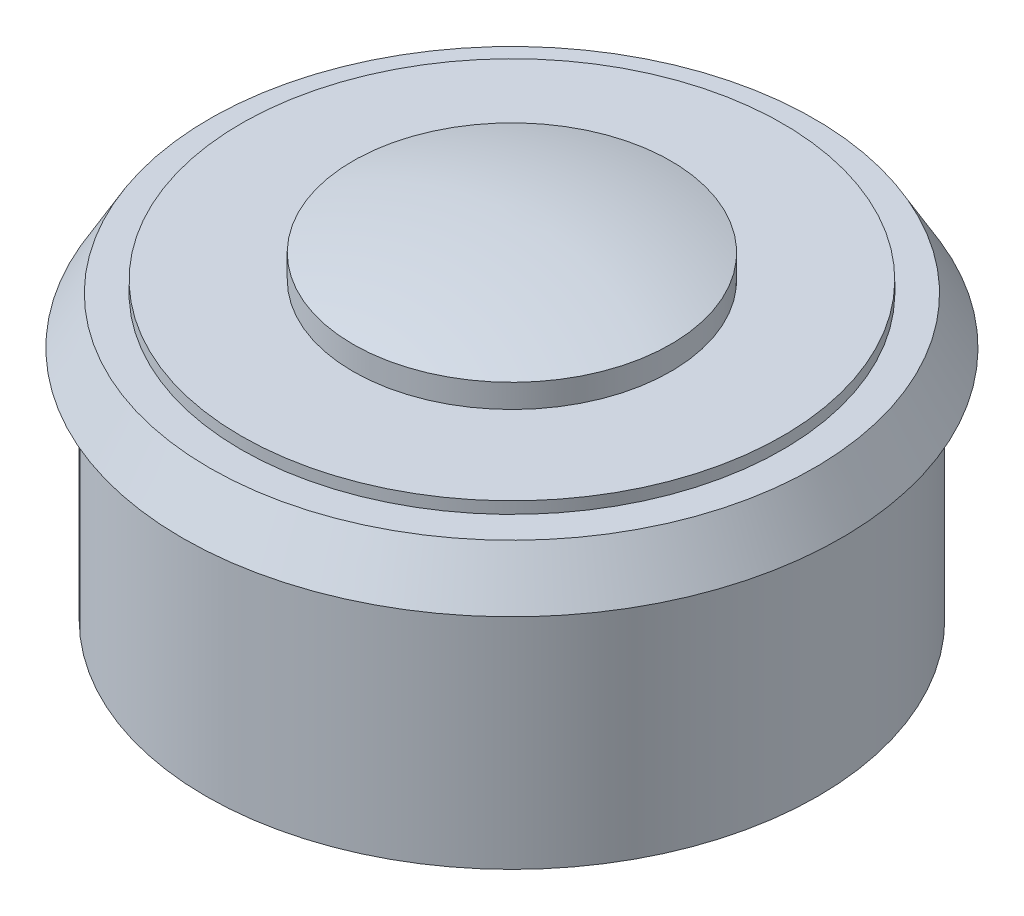
SolidWorks part; units mm, degrees
ref_plane "Front Plane" through (0, 0, 0) normal (0, 0, 1) x (1, 0, 0)
ref_plane "Top Plane" through (0, 0, 0) normal (0, 1, 0) x (1, 0, 0)
ref_plane "Right Plane" through (0, 0, 0) normal (1, 0, 0) x (0, 0, -1)
sketch "Sketch1" plane through (0, 0, 0) normal (0, 1, 0) x (1, 0, 0)
  circle A0 centre (0, 0) radius 13
extrude "Boss-Extrude1" add sketch "Sketch1" along normal blind 10
sketch "Sketch2" plane through (0, 10, 0) normal (0, 1, 0) x (1, 0, 0)
  circle A0 centre (0, 0) radius 14
  dimension "D1" = 28
extrude "Boss-Extrude2" add sketch "Sketch2" along normal blind 2 draft 30 separate body
sketch "Sketch3" plane through (0, 12, 0) normal (0, 1, 0) x (1, 0, 0)
  circle A0 centre (0, 0) radius 11.5
  dimension "D1" = 23
extrude "Boss-Extrude3" add sketch "Sketch3" along normal blind 0.5
sketch "Sketch4" plane through (0, 12.5, 0) normal (0, 1, 0) x (1, 0, 0)
  circle A0 centre (0, 0) radius 6.75
extrude "Boss-Extrude4" add sketch "Sketch4" along normal blind 1
dome "Dome1" faces to dome 1 distance 1 reverse direction no elliptical dome no face at (0, 13.5, 6.75) parameters "D1"=1
